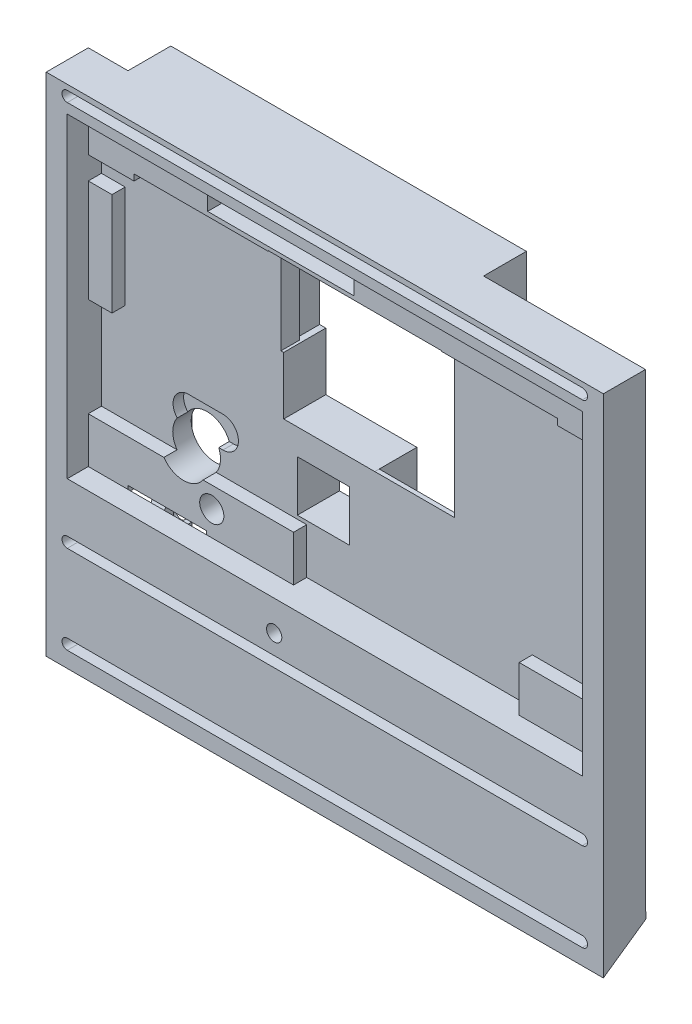
SolidWorks part; units mm, degrees
ref_plane "Front Plane" through (0, 0, 0) normal (0, 0, 1) x (1, 0, 0)
ref_plane "Top Plane" through (0, 0, 0) normal (0, 1, 0) x (1, 0, 0)
ref_plane "Right Plane" through (0, 0, 0) normal (1, 0, 0) x (0, 0, -1)
sketch "Sketch1" plane through (0, 0, 0) normal (0, 0, 1) x (1, 0, 0)
  line L1 (0, 0) -> (67.57, 0)
  line L2 (0, 0) -> (0, 82.04)
  line L3 (0, 82.04) -> (67.57, 82.04)
  line L4 (67.57, 0) -> (67.57, 82.04)
  line L5 (4, 78.04) -> (63.57, 78.04)
  line L6 (4, 78.04) -> (4, 4)
  line L7 (4, 4) -> (63.57, 4)
  line L8 (63.57, 78.04) -> (63.57, 4)
extrude "Boss-Extrude1" add sketch "Sketch1" along normal blind 12.13
sketch "Sketch2" plane through (0, 0, 12.13) normal (0, 0, 1) x (1, 0, 0)
  line L1 (63.57, 4) -> (63.57, 78.04) construction
  line L2 (63.57, 8.81) -> (48.4, 8.81)
  line L6 (21.97, 41.02) -> (27.48, 41.02)
  line L9 (48.4, 41.02) -> (48.4, 8.81)
  line L16 (30.5769, 8.81) -> (18.9086, 8.81)
  line L17 (21.97, 41.02) -> (21.97, 25.27)
  line L18 (21.97, 25.27) -> (30.5769, 25.27)
  line L21 (63.57, 78.04) -> (4, 78.04) construction
  line L22 (46.97, 78.04) -> (46.97, 70.46)
  line L23 (46.97, 69.76) -> (63.57, 69.76)
  line L26 (15, 78.04) -> (15, 71.04)
  line L27 (19.14, 78.04) -> (19.14, 71.04)
  line L30 (4, 78.04) -> (4, 4) construction
  line L35 (4, 52.67) -> (21.97, 52.67)
  line L36 (27.48, 52.67) -> (27.48, 41.02)
  line L37 (31.09, 41.02) -> (48.4, 41.02)
  line L38 (31.09, 42.65) -> (31.09, 41.02)
  line L48 (29.91, 69.76) -> (29.91, 51.9807)
  line L52 (46.97, 78.04) -> (19.14, 78.04)
  line L55 (17.69, 57.7) -> (19.8842, 57.7)
  line L56 (4, 78.04) -> (4, 57.7)
  line L57 (4, 36.69) -> (16.09, 36.69)
  line L58 (4, 30.56) -> (10.54, 30.56)
  line L59 (16.09, 36.69) -> (16.09, 32.69)
  line L60 (30.5769, 25.27) -> (30.5769, 8.81)
  line L61 (18.9086, 8.81) -> (18.9086, 4)
  line L62 (38.121, 16.92) -> (38.121, 8.81)
  line L63 (38.121, 16.92) -> (33.0646, 16.92)
  line L64 (33.0646, 16.92) -> (33.0646, 8.81)
  line L65 (33.0646, 8.81) -> (38.121, 8.81)
  line L66 (43.57, 36.1184) -> (33.6837, 36.1184)
  line L67 (33.6837, 36.1184) -> (33.6837, 26.4902)
  line L68 (43.57, 36.1184) -> (43.57, 26.4902)
  line L69 (43.57, 26.4902) -> (33.6837, 26.4902)
  line L70 (31.09, 42.65) -> (31.09, 51.9807)
  line L71 (31.09, 51.9807) -> (29.91, 51.9807)
  line L72 (17.69, 55.7535) -> (12.049, 55.7535)
  line L73 (12.049, 55.7535) -> (12.049, 53.7)
  line L74 (12.049, 53.7) -> (9.3843, 53.7)
  line L75 (9.3843, 53.7) -> (9.3843, 57.7)
  line L76 (4, 57.7) -> (9.3843, 57.7)
  line L77 (17.69, 55.7535) -> (17.69, 57.7)
  line L78 (19.8842, 57.7) -> (19.8842, 62.1896)
  line L79 (19.8842, 62.1896) -> (23.4, 62.1896)
  line L80 (21.97, 52.67) -> (21.97, 57.9342)
  line L81 (21.97, 57.9342) -> (27.48, 57.9342)
  line L82 (27.48, 57.9342) -> (27.48, 52.67)
  line L84 (46.97, 69.76) -> (29.91, 69.76)
  line L89 (23.4, 65.9748) -> (19.8842, 65.9748)
  line L91 (23.4, 62.1896) -> (23.4, 65.9748)
  line L95 (4, 4) -> (63.57, 4) construction
  line L96 (4, 4) -> (18.9086, 4)
  line L97 (0, 82.04) -> (0, 0)
  line L98 (0, 0) -> (67.57, 0)
  line L99 (67.57, 0) -> (67.57, 82.04)
  line L100 (67.57, 82.04) -> (0, 82.04)
  line L101 (0, 82.04) -> (0, 0)
  line L102 (0, 0) -> (67.57, 0)
  line L103 (67.57, 0) -> (67.57, 82.04)
  line L104 (67.57, 82.04) -> (0, 82.04)
  line L105 (63.57, 8.81) -> (63.57, 69.76)
  line L106 (4, 52.67) -> (4, 36.69)
  line L107 (4, 30.56) -> (4, 4)
  line L108 (15, 78.04) -> (4, 78.04)
  line L110 (19.8842, 70.46) -> (46.97, 70.46)
  line L111 (15, 71.04) -> (19.14, 71.04)
  line L112 (19.8842, 70.46) -> (19.8842, 65.9748)
  arc A1 (16.09, 32.69) -> (10.54, 30.56) centre (14.4372, 28.701) ccw
  line M12 (63.57, 4) -> (4, 4)
  line M13 (4, 4) -> (4, 78.04)
  line M14 (4, 78.04) -> (63.57, 78.04)
  line M15 (63.57, 78.04) -> (63.57, 4)
  dimension "D1" = 0
extrude "Boss-Extrude2" add sketch "Sketch2" against normal blind 10.5 contours L110 L112 L89 L91 L79 L78 L55 L77 L72 L73 L74 L75 L76 L35 L80 L81 L82 L36 L6 L17 L18 L60 L16 L61 L2 L9 L37 L38 L70 L71 L48 L84 L23 L22 L65 L64 L63 L62 L68 L69 L67 L66 M13 M12 M15 M14 | L26 L111 L27 M14 | A1 L59 L57 L58 M13 region at (62.6197, 6.405, 12.13) region at (17.07, 74.54, 12.13) region at (9.4166, 33.9634, 12.13)
sketch "Sketch3" plane through (0, 0, 0) normal (-1, 0, 0) x (0, 0, 1)
  line L8 (0, 82.04) -> (0, 0) construction
  line L12 (0, 68.66) -> (5.07, 68.66)
  line L13 (0, 68.66) -> (0, 60.58)
  line L15 (0, 60.58) -> (5.07, 60.58)
  line L29 (5.07, 60.58) -> (5.07, 68.66)
  circle A2 centre (8.175, 12.315) radius 3.295 construction
  circle A3 centre (8.175, 12.315) radius 3.295
  point P9 (1.63, 7.85)
extrude "Cut-Extrude1" cut sketch "Sketch3" against normal up to surface (4 mm away) up to face at (4, 43.2767, 6.6083)
sketch "Sketch4" plane through (0, 0, 12.13) normal (0, 0, 1) x (1, 0, 0)
  line L1 (4, 78.04) -> (4, 57.7) construction
  line L6 (19.8842, 70.46) -> (46.97, 70.46) construction
  line L18 (18.9086, 8.81) -> (18.9086, 4) construction
  line L34 (4, 70.46) -> (14.8861, 70.46)
  line L35 (19.14, 78.04) -> (19.14, 70.46)
  line L37 (14.8861, 70.46) -> (15, 78.04)
  line L38 (19.14, 70.46) -> (30.5769, 70.46)
  line L39 (15, 78.04) -> (19.14, 78.04)
  line L40 (30.5769, 70.46) -> (30.5769, 4)
  line L41 (4, 4) -> (4, 6.83)
  line L42 (4, 6.83) -> (18.9086, 6.83)
  line L43 (18.9086, 17.8) -> (18.9086, 6.83)
  line L44 (18.9086, 17.8) -> (4, 17.8)
  line L45 (4, 17.8) -> (4, 70.46)
  line L46 (4, 4) -> (30.5769, 4)
  circle A0 centre (14.5441, 28.4224) radius 4.539
  circle A2 centre (19.9197, 21.845) radius 2.2967
extrude "Boss-Extrude3" add sketch "Sketch4" against normal blind 6
sketch "Sketch5" plane through (0, 0, 12.13) normal (0, 0, 1) x (1, 0, 0)
  line L0 (63.57, 8.81) -> (63.57, 69.76) construction
  line L1 (48.4, 8.81) -> (63.57, 8.81)
  line L2 (48.4, 8.81) -> (48.4, 41.0268)
  line L3 (48.4, 41.0268) -> (63.57, 41.0268)
  line L4 (63.57, 8.81) -> (63.57, 41.0268)
sketch "Sketch6" plane through (67.57, 0, 0) normal (1, 0, 0) x (0, 0, -1)
  line L4 (-6.65, 12.72) -> (-2.45, 12.72)
  line L5 (-2.45, 18.62) -> (-2.45, 12.72)
  line L13 (-6.65, 18.62) -> (-2.45, 18.62)
  line L17 (-6.65, 12.72) -> (-6.65, 18.62)
extrude "Cut-Extrude2" cut sketch "Sketch6" against normal up to surface (4 mm away) up to face at (63.57, 40.1525, 3.8475)
extrude "Boss-Extrude5" add sketch "Sketch5" against normal offset from surface (3.33 mm away) 8.8 up to face at (23.19, 48.8867, 0)
sketch "Sketch7" plane through (0, 0, 12.13) normal (0, 0, 1) x (1, 0, 0)
  line L7 (19.54, 30.1429) -> (13.02, 30.1429)
  line L13 (13.02, 36.0371) -> (19.54, 36.0371)
  arc A2 (19.54, 30.1429) -> (19.54, 36.0371) centre (19.54, 33.09) ccw
  arc A3 (13.02, 36.0371) -> (13.02, 30.1429) centre (13.02, 33.09) ccw
  point P9 (10.0051, 32.9614)
extrude "Cut-Extrude3" cut sketch "Sketch7" against normal blind 4.5
sketch "Sketch8" plane through (0, 0, 12.13) normal (0, 0, 1) x (1, 0, 0)
  line L0 (67.57, 82.04) -> (98.33, 82.04)
  line L1 (67.57, 0) -> (67.57, 82.04) construction
  line L2 (-7.54, 82.04) -> (-7.54, 0)
  line L3 (0, 0) -> (0, 82.04)
  line L4 (67.57, 0) -> (67.57, 82.04)
  line L5 (-3.54, 77.14) -> (-3.54, 17.13) construction
  line L6 (0, 82.04) -> (-7.54, 82.04)
  line L8 (-7.54, 0) -> (0, 0)
  line L12 (-3.54, 77.14) -> (-3.54, 17.13)
  line L13 (94.33, 17.13) -> (94.33, 77.14) construction
  line L14 (94.33, 17.13) -> (94.33, 77.14)
  line L15 (-3.54, 17.13) -> (94.33, 17.13) construction
  line L16 (-3.54, 17.13) -> (94.33, 17.13)
  line L17 (94.33, 77.14) -> (-3.54, 77.14) construction
  line L18 (94.33, 77.14) -> (-3.54, 77.14)
  line L19 (-3.54, 17.13) -> (94.33, 17.13) construction
  line L20 (-3.54, 17.13) -> (94.33, 17.13)
  line L22 (67.57, 0) -> (98.33, 0)
  line L23 (98.33, 0) -> (98.33, 82.04)
  line M9 (19.14, 70.46) -> (19.14, 78.04)
  line M10 (19.14, 78.04) -> (46.97, 78.04)
  line M11 (46.97, 78.04) -> (46.97, 70.46)
  line M14 (18.9086, 17.8) -> (18.9086, 6.83)
  line M15 (18.9086, 6.83) -> (4, 6.83)
  line M16 (0, 82.04) -> (0, 0)
  line M17 (0, 0) -> (67.57, 0)
  line M18 (67.57, 0) -> (67.57, 82.04)
  line M19 (67.57, 82.04) -> (0, 82.04)
  line M20 (0, 82.04) -> (0, 0)
  line M21 (4, 78.04) -> (15, 78.04)
  line M24 (4, 70.46) -> (4, 78.04)
  line M25 (38.121, 8.81) -> (33.0646, 8.81)
  line M26 (33.0646, 8.81) -> (33.0646, 16.92)
  line M27 (33.0646, 16.92) -> (38.121, 16.92)
  line M28 (38.121, 16.92) -> (38.121, 8.81)
extrude "Boss-Extrude6" add sketch "Sketch8" against normal blind 4 contours L18 L6 L2 L8 L3 L16 L12 M20 M16 | L3 L18 L12 L16 | L22 L23 L0 L18 L14 L16 M18 | L14 L18 L4 L16 region at (82.95, 81.1638, 12.13) region at (80.95, 47.135, 12.13) region at (-4.8161, 37.8215, 12.13) region at (-1.77, 47.135, 12.13)
extrude "Boss-Extrude7" add sketch "Sketch8<3>" along normal blind 4 contours L18 L6 L2 L8 L3 L16 L12 M20 M16 | L16 M14 M15 M16 M17 M18 M28 M25 M26 M27 | L22 L23 L0 L18 L14 L16 M18 | L18 M18 M19 M20 M24 M21 M9 M10 M11 | L18 M21 M24 | L18 M11 M10 M9 | M25 M28 M27 M26 | L16 L3 M15 M14 region at (82.95, 81.1638, 12.13) region at (33.8447, 79.7537, 12.13) region at (-4.8161, 37.8215, 12.13) region at (33.7186, 8.4071, 12.13) region at (33.055, 77.59, 12.13) region at (35.5928, 12.865, 12.13)
sketch "Sketch8<3>" plane through (0, 0, 12.13) normal (0, 0, 1) x (1, 0, 0) same geometry as "Sketch8"
sketch "Sketch9" plane through (0, 0, 16.13) normal (0, 0, 1) x (1, 0, 0)
  circle A1 centre (35.7805, 11.382) radius 1.4494
extrude "Cut-Extrude4" cut sketch "Sketch9" against normal up to surface (14.5 mm away) up to face at (35.5928, 12.865, 1.63)
sketch "Sketch10" plane through (0, 0, 12.13) normal (0, 0, 1) x (1, 0, 0)
  line L1 (-3.54, 77.14) -> (-3.54, 17.13) construction
  line L4 (-3.54, 68.45) -> (5.15, 68.45)
  line L5 (5.15, 68.45) -> (5.15, 69.64)
  line L6 (-3.54, 68.45) -> (-3.54, 64.13)
  line L7 (-3.54, 25.82) -> (35.46, 25.82)
  line L8 (5.15, 69.64) -> (85.64, 69.64)
  line L9 (85.64, 69.64) -> (85.64, 68.45)
  line L12 (85.64, 68.45) -> (94.33, 68.45)
  line L21 (35.46, 17.13) -> (35.46, 25.82)
  line L24 (78.33, 17.13) -> (78.33, 25.82)
  line L25 (78.33, 25.82) -> (94.33, 25.82)
  line L26 (94.33, 68.45) -> (94.33, 47.135)
  line L27 (0.96, 64.13) -> (0.96, 44.63)
  line L28 (91.33, 35.13) -> (91.33, 47.135)
  line L29 (94.33, 35.13) -> (94.33, 25.82)
  line L30 (91.33, 57.13) -> (91.33, 35.13)
  line L31 (91.33, 57.13) -> (94.33, 57.13)
  line L32 (91.33, 35.13) -> (94.33, 35.13)
  line L33 (0.96, 64.13) -> (-3.54, 64.13)
  line L34 (0.96, 44.63) -> (-3.54, 44.63)
  line L35 (-3.54, 44.63) -> (-3.54, 25.82)
  line M6 (63.57, 69.76) -> (63.57, 41.0268)
  line M7 (63.57, 41.0268) -> (48.4, 41.0268)
  line M8 (48.4, 41.0268) -> (48.4, 41.02)
  line M9 (48.4, 41.02) -> (31.09, 41.02)
  line M10 (31.09, 41.02) -> (31.09, 51.9807)
  line M11 (31.09, 51.9807) -> (30.5769, 51.9807)
  line M12 (30.5769, 51.9807) -> (30.5769, 69.76)
  line M20 (-3.54, 77.14) -> (-3.54, 17.13)
  line M25 (18.9086, 17.13) -> (94.33, 17.13)
  line M26 (94.33, 17.13) -> (94.33, 77.14)
  line M30 (43.57, 36.1184) -> (43.57, 26.4902)
  line M31 (43.57, 26.4902) -> (33.6837, 26.4902)
  line M32 (33.6837, 26.4902) -> (33.6837, 36.1184)
  line M33 (33.6837, 36.1184) -> (43.57, 36.1184)
  arc M34 (19.54, 36.0371) -> (19.54, 30.1429) centre (19.54, 33.09) cw
  line M35 (19.54, 30.1429) -> (18.7444, 30.1429)
  arc M36 (18.7444, 30.1429) -> (10.8646, 31.0801) centre (14.5441, 28.4224) cw
  arc M37 (10.8646, 31.0801) -> (13.02, 36.0371) centre (13.02, 33.09) cw
  line M38 (13.02, 36.0371) -> (19.54, 36.0371)
extrude "Cut-Extrude5" cut sketch "Sketch10" against normal blind 2.5 contours L27 L34 L7 L21 L24 L25 L32 L28 L30 L31 L26 L12 L9 L8 L5 L4 L33 M20 M36 M37 M38 M34 M35 M25 M26 M6 M7 M8 M9 M10 M11 M12 M33 M30 M31 M32 region at (0.805, 67.3393, 12.13)
sketch "Sketch11" plane through (0, 0, 0) normal (0, 0, -1) x (-1, 0, 0)
  line L2 (-2.5646, 5.695) -> (-2.5646, 16.665)
  line L4 (-18.9086, 16.665) -> (-18.9086, 5.695)
  line L7 (-2.5646, 5.695) -> (-18.9086, 5.695)
  line L8 (-18.9086, 16.665) -> (-2.5646, 16.665)
extrude "Cut-Extrude6" cut sketch "Sketch11" against normal blind 12.78
sketch "Sketch12" plane through (-7.54, 0, 0) normal (-1, 0, 0) x (0, 0, 1)
  circle A2 centre (8.13, 11.18) radius 5
extrude "Cut-Extrude7" cut sketch "Sketch12" against normal up to surface (10.1046 mm away) up to face at (2.5646, 11.18, 6.39)
sketch "Sketch13" plane through (0, 0, 0) normal (-1, 0, 0) x (0, 0, 1)
  line L0 (6.1, 59.12) -> (0.6, 59.12)
  line L1 (6.1, 70.12) -> (6.1, 59.12)
  line L2 (6.1, 70.12) -> (0.6, 70.12)
  line L3 (0.6, 59.12) -> (0.6, 70.12)
  point P14 (6.8339, 64.62)
extrude "Cut-Extrude8" cut sketch "Sketch13" against normal blind 2
chamfer "Chamfer1" distance 2 angle 10 5 edges at (0, 59.85, 0.6) (0, 69.39, 0.6) (0, 70.12, 3.35) (0, 59.12, 3.35) (0, 64.62, 6.1) first distance on face at (1, 59.85, 0.6) first distance on face at (1, 69.39, 0.6) first distance on face at (1, 70.12, 3.35) first distance on face at (1, 59.12, 3.35) first distance on face at (1, 64.62, 6.1)
sketch "Sketch15" plane through (67.57, 0, 0) normal (1, 0, 0) x (0, 0, -1)
  line L0 (-8.13, 9.5139) -> (-8.13, 21.8261)
  line L1 (-8.13, 0) -> (-8.13, 82.04) construction
  line L4 (0, 0) -> (0, 82.04) construction
  line L9 (0, 9.5139) -> (0, 21.8261)
  line L10 (-8.13, 9.5139) -> (0, 9.5139)
  line L11 (-8.13, 21.8261) -> (0, 21.8261)
extrude "Cut-Extrude9" cut sketch "Sketch15" against normal blind 3.75
chamfer "Chamfer2" distance 4 angle 60 2 edges at (67.57, 21.8261, 4.065) (67.57, 9.5139, 4.065) first distance on face at (65.695, 21.8261, 4.065) first distance on face at (65.695, 9.5139, 4.065)
fillet "Fillet1" radius 10 2 edges at (67.57, 28.7543, 4.065) (67.57, 2.5857, 4.065)
sketch "Sketch18" plane through (0, 0, 0) normal (0, 0, -1) x (-1, 0, 0)
  line L11 (-65.57, 81.04) -> (-2, 81.04)
  line L15 (-66.57, 28.9939) -> (-66.57, 74.5887)
  line L16 (-65.57, 1) -> (-2, 1)
  line L17 (-65.57, 79.04) -> (-2, 79.04)
  line L18 (-65.57, 3) -> (-2, 3)
  line L19 (-64.57, 28.9939) -> (-64.57, 74.5887)
  line L20 (-3, 6.1098) -> (-3, 57.7673)
  line L21 (-1, 6.1098) -> (-1, 57.7673)
  line L29 (-1, 71.4727) -> (-1, 74.5887)
  line L30 (-3, 71.4727) -> (-3, 74.5887)
  arc A16 (-65.57, 3) -> (-65.57, 1) centre (-65.57, 2) ccw
  arc A17 (-2, 1) -> (-2, 3) centre (-2, 2) ccw
  arc A18 (-2, 79.04) -> (-2, 81.04) centre (-2, 80.04) ccw
  arc A19 (-65.57, 81.04) -> (-65.57, 79.04) centre (-65.57, 80.04) ccw
  arc A20 (-1, 74.5887) -> (-3, 74.5887) centre (-2, 74.5887) ccw
  arc A21 (-3, 6.1098) -> (-1, 6.1098) centre (-2, 6.1098) ccw
  arc A22 (-64.57, 74.5887) -> (-66.57, 74.5887) centre (-65.57, 74.5887) ccw
  arc A23 (-66.57, 28.9939) -> (-64.57, 28.9939) centre (-65.57, 28.9939) ccw
  arc A24 (-3, 71.4727) -> (-1, 71.4727) centre (-2, 71.4727) ccw
  arc A25 (-1, 57.7673) -> (-3, 57.7673) centre (-2, 57.7673) ccw
extrude "Cut-Extrude10" cut sketch "Sketch18" against normal blind 2
sketch "Sketch21" plane through (0, 0, 0) normal (-1, 0, 0) x (0, 0, 1)
  line L1 (16.13, 0) -> (0, 0)
  line L2 (16.13, 0) -> (16.13, -14.1)
  line L3 (0, 0) -> (0, -2.8)
  line L4 (0, -2.8) -> (16.13, -14.1)
  line L7 (8.13, 0) -> (8.065, -8.45)
  line M5 (0, 0) -> (8.13, 0)
extrude "Boss-Extrude8" add sketch "Sketch21" along normal up to surface and the other way up to surface contours L1 L7 L4 L2 region at (0, -5.7644, 12.4475) up to face at (-7.54, 31.0733, 11.63) other way up to face at (98.33, 41.02, 12.13)
extrude "Boss-Extrude9" add sketch "Sketch21<3>" against normal up to surface (67.57 mm away) contours L7 L3 L4 M5 region at (0, -3.0476, 4.7279) up to face at (67.57, 56.7369, 4.065)
sketch "Sketch21<3>" plane through (0, 0, 0) normal (-1, 0, 0) x (0, 0, 1) same geometry as "Sketch21"
sketch "Sketch22" plane through (0, 0, 0) normal (-1, 0, 0) x (0, 0, 1)
  line L2 (1.63, 74.54) -> (8.13, 74.54) construction
  line L3 (8.13, 82.04) -> (8.13, 16.18) construction
  circle A0 centre (4.88, 74.54) radius 1
extrude "Cut-Extrude11" cut sketch "Sketch22" against normal blind 15
sketch "Sketch23" plane through (0, 78.04, 0) normal (0, -1, 0) x (1, 0, 0)
  line L0 (15, 12.13) -> (15, 2.9095)
  line L1 (4, 12.13) -> (15, 12.13)
  line L2 (0, 4.88) -> (12.8322, 4.88) construction
  line L3 (15, 12.13) -> (4, 12.13) construction
  line L5 (15, 1.63) -> (15, 6.13) construction
  line L7 (4, 12.13) -> (4, 0) construction
  line L8 (4, 9.0473) -> (4, 12.13)
  line L9 (4, 9.0473) -> (15, 2.9095)
extrude "Boss-Extrude10" add sketch "Sketch23" along normal up to surface (7.58 mm away) up to face at (9.443, 70.46, 9.13)
ref_plane "Plane1" through (2, 0, -2) normal (0.7071, 0, -0.7071) x (0, -1, 0)
sketch "Sketch24" plane through (2, 0, -2) normal (0.7071, 0, -0.7071) x (0, -1, 0)
  line L0 (-73.54, -4.8649) -> (-73.54, -6.2791)
  line L1 (-75.54, -4.8649) -> (-75.54, -6.2791)
  ellipse E1 centre (-74.54, -6.2791) end of major axis (-73.54, -6.2791) minor radius 0.7071 (-75.54, -6.2791) -> (-73.54, -6.2791) ccw
  ellipse E2 centre (-74.54, -4.8649) end of major axis (-73.54, -4.8649) minor radius 0.7071 (-73.54, -4.8649) -> (-75.54, -4.8649) ccw
extrude "Cut-Extrude14" cut sketch "Sketch24" against normal up to next
sketch "Sketch25" plane through (0, 0, 0) normal (0, 0, -1) x (-1, 0, 0)
  line L0 (-4, 75.54) -> (-4, 73.54) construction
  line L1 (-4, 75.54) -> (-4, 73.54)
  line L2 (-4, 73.54) -> (-15, 73.54)
  line L3 (-15, 71.04) -> (-15, 78.04) construction
  line L4 (-15, 73.54) -> (-15, 75.54)
  line L5 (-4, 75.54) -> (-15, 75.54)
extrude "Cut-Extrude15" cut sketch "Sketch25" against normal up to vertex (9.0473 mm away) up to point (4, 70.46, 9.0473)
sketch "Sketch28" plane through (0, 0, 16.13) normal (0, 0, 1) x (1, 0, 0)
  line L4 (-3.54, 79.04) -> (94.33, 79.04)
  line L5 (94.33, 81.04) -> (-3.54, 81.04)
  line L6 (-3.54, 79.04) -> (94.33, 79.04)
  line L7 (94.33, 81.04) -> (-3.54, 81.04)
  line L10 (94.33, -9.1) -> (-3.54, -9.1)
  line L11 (-3.54, -11.1) -> (94.33, -11.1)
  line L12 (-3.54, 5.6793) -> (94.33, 5.6793)
  line L13 (94.33, 7.6793) -> (-3.54, 7.6793)
  line L14 (-3.54, 5.6793) -> (94.33, 5.6793)
  line L15 (94.33, 7.6793) -> (-3.54, 7.6793)
  arc A2 (-3.54, 81.04) -> (-3.54, 79.04) centre (-3.54, 80.04) ccw
  arc A3 (94.33, 79.04) -> (94.33, 81.04) centre (94.33, 80.04) ccw
  arc A4 (-3.54, 81.04) -> (-3.54, 79.04) centre (-3.54, 80.04) ccw
  arc A5 (94.33, 79.04) -> (94.33, 81.04) centre (94.33, 80.04) ccw
  arc A8 (94.33, -11.1) -> (94.33, -9.1) centre (94.33, -10.1) ccw
  arc A9 (-3.54, -9.1) -> (-3.54, -11.1) centre (-3.54, -10.1) ccw
  arc A10 (-3.54, 7.6793) -> (-3.54, 5.6793) centre (-3.54, 6.6793) ccw
  arc A11 (94.33, 5.6793) -> (94.33, 7.6793) centre (94.33, 6.6793) ccw
  arc A12 (-3.54, 7.6793) -> (-3.54, 5.6793) centre (-3.54, 6.6793) ccw
  arc A13 (94.33, 5.6793) -> (94.33, 7.6793) centre (94.33, 6.6793) ccw
  dimension "D1" = 0
  dimension "D3" = 0
extrude "Cut-Extrude17" cut sketch "Sketch28" against normal blind 2
